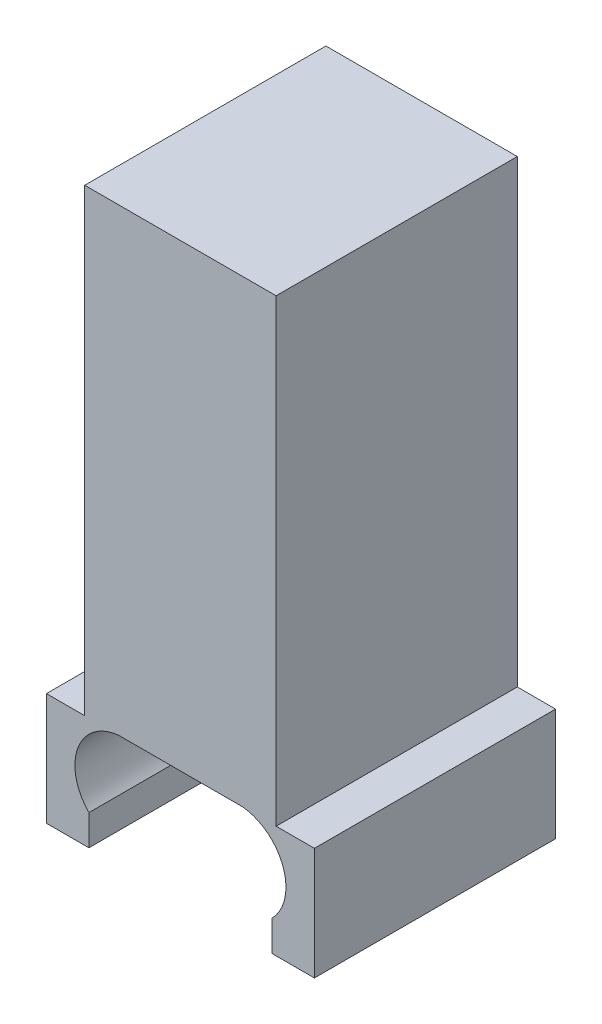
SolidWorks part; units mm, degrees
ref_plane "Front Plane" through (0, 0, 0) normal (0, 0, 1) x (1, 0, 0)
ref_plane "Top Plane" through (0, 0, 0) normal (0, 1, 0) x (1, 0, 0)
ref_plane "Right Plane" through (0, 0, 0) normal (1, 0, 0) x (0, 0, -1)
sketch "Sketch1" plane through (0, 0, 0) normal (1, 0, 0) x (0, 0, -1)
  line L0 (-40, 30) -> (0, 30)
  line L1 (-40, 30) -> (-40, 34)
  line L2 (-40, 34) -> (0, 34)
  line L3 (0, 34) -> (0, 50)
  line L4 (0, 50) -> (31.5, 50)
  line L5 (31.5, 50) -> (31.5, 40)
  line L6 (31.5, 40) -> (4, 40)
  line L7 (4, 40) -> (4, 0)
  line L8 (4, 0) -> (31.5, 0)
  line L9 (31.5, 0) -> (31.5, -10)
  line L10 (31.5, -10) -> (0, -10)
  line L11 (0, -10) -> (0, 30)
  line L12 (4, 30) -> (31.5, 30) construction
  line L13 (4, 0) -> (0, 0) construction
  line L14 (31.5, 40) -> (31.5, 0)
  line L15 (0, 34) -> (0, 30)
  dimension "D1" = 40
  dimension "D2" = 40
  dimension "D3" = 27.5
  dimension "D4" = 10
  dimension "D5" = 60
  dimension "D6" = 4
extrude "Boss-Extrude1" add sketch "Sketch1" along normal mid plane 25 contours L14 L6 L7 L8 | L11 L10 L9 L8 L7 L6 L5 L4 L3 L2 L1 L0 region at (0, 32, -0.6777) region at (0, 20, -17.75)
sketch "Sketch7" plane through (0, -10, 0) normal (0, -1, 0) x (1, 0, 0)
  line L0 (12.5, 0) -> (-12.5, 0) construction
  line L1 (-26.0759, 0) -> (26.0759, 0)
  line L2 (-26.0759, 0) -> (-26.0759, -31.5)
  line L3 (-26.0759, -31.5) -> (26.0759, -31.5)
  line L4 (26.0759, 0) -> (26.0759, -31.5)
  line L5 (12.5, -31.5) -> (-12.5, -31.5) construction
  line L6 (0, 0) -> (0, -31.5) construction
  line L7 (-26.0759, -15.75) -> (26.0759, -15.75) construction
  circle A0 centre (-17.5, -4.6604) radius 1.8978
  circle A2 centre (-17.5, -26.8396) radius 1.8978
  circle A3 centre (17.5, -26.8396) radius 1.8978
  circle A4 centre (17.5, -4.6604) radius 1.8978
  dimension "D1" = 35
extrude "Boss-Extrude2" [suppressed] add sketch "Sketch7" against normal blind 4
sketch "Sketch2" plane through (0, 0, -31.5) normal (0, 0, -1) x (-1, 0, 0)
  line L0 (10.015, 40.015) -> (10.015, 50) construction
  line L1 (10.015, -0.015) -> (-10.015, -0.015)
  line L2 (10.015, -0.015) -> (10.015, 40.015)
  line L3 (10.015, 40.015) -> (-10.015, 40.015)
  line L4 (-10.015, -0.015) -> (-10.015, 40.015)
  line L5 (10.015, -0.015) -> (-10.015, 40.015) construction
  line L6 (10.015, 40.015) -> (-10.015, -0.015) construction
  line L7 (-12.5, 50) -> (12.5, 50) construction
  line L8 (10.015, -0.015) -> (10.015, -10) construction
  line L9 (-12.5, -10) -> (12.5, -10) construction
  line L11 (5, -4) -> (-5, -4)
  line L12 (5, -4) -> (5, 44)
  line L13 (5, 44) -> (-5, 44)
  line L14 (-5, -4) -> (-5, 44)
  line L15 (5, -4) -> (-5, 44) construction
  line L16 (5, 44) -> (-5, -4) construction
  point P0 (0, 20)
  point P16 (0, 20)
  dimension "D1" = 40.03
  dimension "D2" = 20.03
  dimension "D3" = 48
  dimension "D4" = 10
extrude "Cut-Extrude1" cut sketch "Sketch2" against normal mid plane 27.53 contours L12 L1 L2 L3 | L14 L1 L12 L3 | L1 L14 L3 L4 region at (-7.5075, 20, -31.5) region at (0, 20, -31.5) region at (7.5075, 20, -31.5)
sketch "Sketch6" plane through (0, 0, -31.5) normal (0, 0, -1) x (-1, 0, 0)
  circle A0 centre (-5, 44) radius 3.25
  circle A1 centre (5, 44) radius 3.25
  circle A2 centre (5, -4) radius 3.25
  circle A3 centre (-5, -4) radius 3.25
  dimension "D1" = 6.5
extrude "Cut-Extrude2" cut sketch "Sketch6" against normal blind 12
sketch "Sketch9" plane through (0, 0, -31.5) normal (0, 0, -1) x (-1, 0, 0)
  line L0 (-12.5, -10) -> (12.5, -10) construction
  line L1 (11.9194, -20.6694) -> (11.9194, -24.6694)
  line L2 (11.9194, -24.6694) -> (0, -24.6694)
  line L3 (0, -24.6694) -> (0, 0) construction
  line L4 (7.5, -10) -> (0, -10)
  line L5 (7.5, -9.97) -> (0, -9.97)
  line L6 (11.9494, -20.6818) -> (11.9494, -24.6994)
  line L7 (11.9494, -24.6694) -> (17.5, -24.6694)
  line L8 (8.1131, -10) -> (17.5, -10)
  line L9 (17.5, -24.6694) -> (17.5, -10)
  line L10 (11.9494, -24.6994) -> (0, -24.6994) construction
  line L11 (-8.1131, -10) -> (-17.5, -10)
  line L12 (-11.9494, -20.6818) -> (-11.9494, -24.6994)
  line L13 (-17.5, -24.6694) -> (-17.5, -10)
  line L14 (-11.9494, -24.6694) -> (-17.5, -24.6694)
  line L15 (11.9194, -20.6694) -> (10.4978, -22.091) construction
  line L16 (0, -24.6694) -> (-11.9494, -24.6694)
  line L17 (11.9194, -24.6694) -> (11.9494, -24.6694)
  line L18 (-7.5, -9.97) -> (0, -10)
  arc A0 (7.5, -10) -> (11.9194, -20.6694) centre (7.5, -16.25) cw
  arc A1 (7.5, -9.97) -> (11.9494, -20.6818) centre (7.5, -16.25) cw
  arc A2 (-7.5, -9.97) -> (-11.9494, -20.6818) centre (-7.5, -16.25) ccw
  point P21 (0, 0)
  line M24 (-12.5, -10) -> (12.5, -10)
  dimension "D2" = 6.25
  dimension "D1" = 4
  dimension "D4" = 15
  dimension "D5" = 45
  dimension "D6" = 10
  dimension "D3" = 0.03
extrude "Boss-Extrude5" add sketch "Sketch9" against normal up to surface (31.5 mm away) contours A2 L13 L14 L12 M24 | A1 L6 L7 L9 M24 region at (-14.9099, -17.2736, -31.5) region at (14.9099, -17.2736, -31.5) up to face at (0, 20, 0)
extrude "Boss-Extrude6" add sketch "Sketch9<4>" against normal blind 2 contours A2 L12 L16 L2 L1 A0 M24 | A2 L18 | A1 A0 L1 L17 L6 M24 | L18 A2 M24 region at (-13.289, -13.8521, -31.5) region at (0.0181, -17.3605, -31.5) region at (-3.75, -9.35, -31.5) region at (5.2684, -9.9898, -31.5)
sketch "Sketch9<4>" plane through (0, 0, -31.5) normal (0, 0, -1) x (-1, 0, 0) same geometry as "Sketch9"
sketch "Sketch10" plane through (0, 0, -29.5) normal (0, 0, 1) x (1, 0, 0)
  circle A0 centre (-7.5, -16.25) radius 1.6
  circle A1 centre (7.5, -16.25) radius 1.6
  point P4 (0, 0)
  dimension "D1" = 3.2
extrude "Cut-Extrude3" cut sketch "Sketch10" against normal through all both and the other way through all
